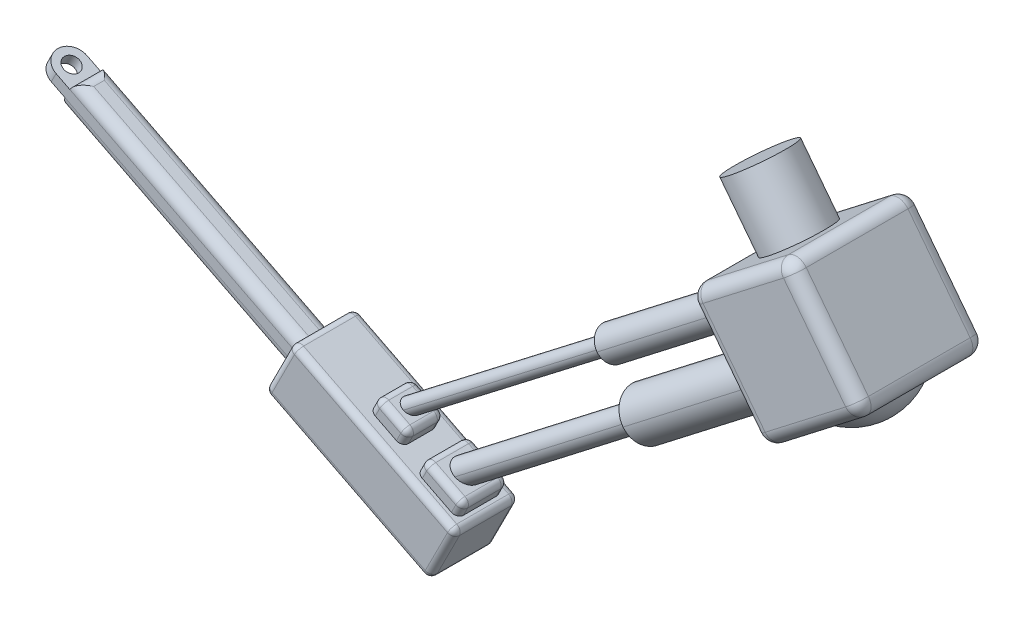
SolidWorks part; units mm, degrees
ref_plane "Front Plane" through (0, 0, 0) normal (0, 0, 1) x (1, 0, 0)
ref_plane "Top Plane" through (0, 0, 0) normal (0, 1, 0) x (1, 0, 0)
ref_plane "Right Plane" through (0, 0, 0) normal (1, 0, 0) x (0, 0, -1)
sketch "Sketch2" plane through (0, 0, 0) normal (0, 0, 1) x (1, 0, 0)
  line L0 (226.5457, 190.9655) -> (147.403, 129.839) construction
  line L1 (147.403, 129.839) -> (-96.781, -58.7584) construction
  line L2 (86.2766, 208.9817) -> (208.5294, 50.6964)
  line L3 (-96.781, -58.7584) -> (147.403, 129.839)
  line L4 (147.403, 129.839) -> (193.2478, 70.4821)
  line L5 (193.2478, 70.4821) -> (-50.9362, -118.1154)
  line L6 (208.5294, 50.6964) -> (366.8147, 172.9493)
  line L7 (-112.0626, -38.9727) -> (132.1214, 149.6247)
  line L8 (132.1214, 149.6247) -> (101.5582, 189.196)
  line L9 (101.5582, 189.196) -> (-142.6258, 0.5986)
  line L10 (366.8147, 172.9493) -> (244.5619, 331.2346)
  line L11 (244.5619, 331.2346) -> (86.2766, 208.9817)
  line L12 (-456.7039, -257.0363) -> (-470.0861, -250.2602)
  line L13 (-338.7843, -316.7457) -> (-62.3974, -103.2761)
  line L14 (-62.3974, -103.2761) -> (-50.9362, -118.1154)
  line L15 (-50.9362, -118.1154) -> (-62.3974, -103.2761)
  line L16 (-432.294, -269.3964) -> (-456.7039, -257.0363)
  line L18 (-134.985, -9.2942) -> (-142.6258, 0.5986)
  line L19 (-85.3198, -73.5976) -> (-96.781, -58.7584)
  line L20 (-112.0626, -38.9727) -> (-119.7034, -29.0799)
  line L21 (193.2478, 70.4821) -> (-50.9362, -118.1154)
  line L22 (193.2478, 70.4821) -> (-50.9362, -118.1154)
  line L23 (-62.3974, -103.2761) -> (-338.7843, -316.7457)
  line L24 (-96.781, -58.7584) -> (147.403, 129.839)
  line L26 (-62.3974, -103.2761) -> (-85.3198, -73.5976)
  line L27 (-119.7034, -29.0799) -> (-134.985, -9.2942)
  line L38 (226.5457, 190.9655) -> (231.3859, -316.7457) construction
  line L39 (-338.7843, -316.7457) -> (231.3859, -316.7457) construction
  line L41 (-85.3198, -73.5976) -> (-375.7062, -298.05)
  line L45 (-119.7034, -29.0799) -> (-432.294, -269.3964)
  line L50 (-375.7062, -298.05) -> (-389.0884, -291.2739)
  line L51 (-134.985, -9.2942) -> (-456.7039, -257.0363)
  line L52 (-456.7039, -257.0363) -> (-470.0861, -250.2602)
  line L53 (-470.0861, -250.2602) -> (-481.3797, -272.5638)
  line L54 (-481.3797, -272.5638) -> (-430.2055, -298.4763)
  line L55 (-430.2055, -298.4763) -> (-418.9118, -276.1726)
  line L56 (-418.9118, -276.1726) -> (-432.294, -269.3964)
  line L57 (-389.0884, -291.2739) -> (-400.382, -313.5775)
  line L58 (-400.382, -313.5775) -> (-336.6957, -345.8255)
  line L59 (-336.6957, -345.8255) -> (-325.4021, -323.5218)
  line L60 (-325.4021, -323.5218) -> (-338.7843, -316.7457)
  line L61 (-418.9118, -276.1726) -> (-432.294, -269.3964)
  line L63 (-338.7843, -316.7457) -> (-375.7062, -298.05)
  dimension "D2" = 50
  dimension "D3" = 75
  dimension "D4" = 50
  dimension "D5" = 37.5
  dimension "D6" = 18.75
  dimension "D7" = 25
  dimension "D8" = 12.5
  dimension "D9" = 507.7112
  dimension "D10" = 570.1702
  dimension "D11" = 15
  dimension "D12" = 15
  dimension "D13" = 15
  dimension "D17" = 25
  dimension "D18" = 25
  dimension "D19" = 25
  dimension "D20" = 15
extrude "Boss-Extrude1" add sketch "Sketch2" along normal blind 100 contours L10 L11 L2 L6 region at (226.5457, 190.9655, 0)
extrude "Boss-Extrude2" add sketch "Sketch2<3>" against normal blind 100 contours L10 L11 L2 L6 region at (226.5457, 190.9655, 0)
sketch "Sketch2<3>" plane through (0, 0, 0) normal (0, 0, 1) x (1, 0, 0) same geometry as "Sketch2"
extrude "Boss-Extrude3" add sketch "Sketch2<4>" along normal blind 25 contours L27 L20 L7 L2 L9 L18 region at (-5.2522, 75.1117, 0)
sketch "Sketch2<4>" plane through (0, 0, 0) normal (0, 0, 1) x (1, 0, 0) same geometry as "Sketch2"
extrude "Boss-Extrude4" add sketch "Sketch2<5>" along normal blind 12.5 contours L27 region at (-285.6315, -140.9012, 0)
sketch "Sketch2<5>" plane through (0, 0, 0) normal (0, 0, 1) x (1, 0, 0) same geometry as "Sketch2"
extrude "Boss-Extrude5" add sketch "Sketch2<6>" against normal blind 25 contours L27 L20 L7 L2 L9 L18 region at (-5.2522, 75.1117, 0)
sketch "Sketch2<6>" plane through (0, 0, 0) normal (0, 0, 1) x (1, 0, 0) same geometry as "Sketch2"
extrude "Boss-Extrude6" add sketch "Sketch2<7>" against normal blind 12.5 contours L27 region at (-285.6315, -140.9012, 0)
sketch "Sketch2<7>" plane through (0, 0, 0) normal (0, 0, 1) x (1, 0, 0) same geometry as "Sketch2"
extrude "Boss-Extrude7" add sketch "Sketch2<8>" along normal blind 37.5 contours L26 L14 L5 L2 L3 L19 region at (48.2334, 5.8618, 0)
sketch "Sketch2<8>" plane through (0, 0, 0) normal (0, 0, 1) x (1, 0, 0) same geometry as "Sketch2"
extrude "Boss-Extrude8" add sketch "Sketch2<9>" against normal blind 37.5 contours L26 L14 L5 L2 L3 L19 region at (48.2334, 5.8618, 0)
sketch "Sketch2<9>" plane through (0, 0, 0) normal (0, 0, 1) x (1, 0, 0) same geometry as "Sketch2"
extrude "Boss-Extrude9" add sketch "Sketch2<10>" along normal blind 18.75 contours L26 L13 region at (-215.5932, -197.753, 0)
sketch "Sketch2<10>" plane through (0, 0, 0) normal (0, 0, 1) x (1, 0, 0) same geometry as "Sketch2"
extrude "Boss-Extrude10" add sketch "Sketch2<11>" against normal blind 18.75 contours L26 L13 region at (-215.5932, -197.753, 0)
sketch "Sketch2<11>" plane through (0, 0, 0) normal (0, 0, 1) x (1, 0, 0) same geometry as "Sketch2"
sketch3d "3DSketch1"
  point P0 (182.6105, 283.386, 58.542)
ref_plane "Plane1" through (-68.8625, 89.1588, 0) normal (-0.6113, 0.7914, 0) x (0.7914, 0.6113, 0)
sketch "Sketch3" plane through (-68.8625, 89.1588, 0) normal (-0.6113, 0.7914, 0) x (0.7914, 0.6113, 0)
  line L0 (296.0246, 100) -> (296.0246, -100) construction
  line L1 (396.0246, 100) -> (196.0246, 100) construction
  line L2 (396.0246, -100) -> (196.0246, -100) construction
  line L3 (396.0246, 0) -> (196.0246, 0) construction
  line L4 (396.0246, -100) -> (396.0246, 100) construction
  line L5 (196.0246, -100) -> (196.0246, 100) construction
  circle A0 centre (296.0246, 0) radius 50
  dimension "D2" = 100
  dimension "D1" = 100
extrude "Boss-Extrude15" add sketch "Sketch3" along normal blind 100
sketch3d "3DSketch2"
  point P0 (295.099, 117.559, -29.7433)
ref_plane "Plane2" through (53.3904, -69.1265, 0) normal (0.6113, -0.7914, 0) x (0.7914, 0.6113, 0)
sketch "Sketch4" plane through (53.3904, -69.1265, 0) normal (0.6113, -0.7914, 0) x (0.7914, 0.6113, 0)
  line L0 (296.0246, 100) -> (296.0246, -100) construction
  line L1 (196.0246, 100) -> (396.0246, 100) construction
  line L2 (196.0246, -100) -> (396.0246, -100) construction
  line L3 (396.0246, 0) -> (196.0246, 0) construction
  line L4 (396.0246, 100) -> (396.0246, -100) construction
  line L5 (196.0246, 37.5) -> (196.0246, -37.5) construction
  circle A0 centre (296.0246, 0) radius 62.5
  dimension "D1" = 125
extrude "Boss-Extrude16" add sketch "Sketch4" along normal blind 25
fillet "Fillet1" radius 90 1 edges at (352.4179, 130.2412, 0)
extrude "Boss-Extrude17" add sketch "Sketch2<19>" along normal blind 28.75 contours L55 L56 L16 L12 L53 L54 region at (-450.1458, -274.3682, 0)
sketch "Sketch2<19>" plane through (0, 0, 0) normal (0, 0, 1) x (1, 0, 0) same geometry as "Sketch2"
extrude "Boss-Extrude18" add sketch "Sketch2<20>" against normal blind 28.75 contours L55 L56 L16 L12 L53 L54 region at (-450.1458, -274.3682, 0)
sketch "Sketch2<20>" plane through (0, 0, 0) normal (0, 0, 1) x (1, 0, 0) same geometry as "Sketch2"
extrude "Boss-Extrude19" add sketch "Sketch2<21>" along normal blind 35.75 contours L60 L63 L50 L57 L58 L59 region at (-362.8921, -318.5497, 0)
sketch "Sketch2<21>" plane through (0, 0, 0) normal (0, 0, 1) x (1, 0, 0) same geometry as "Sketch2"
extrude "Boss-Extrude20" add sketch "Sketch2<22>" against normal blind 35.75 contours L60 L63 L50 L57 L58 L59 region at (-362.8921, -318.5497, 0)
sketch "Sketch2<22>" plane through (0, 0, 0) normal (0, 0, 1) x (1, 0, 0) same geometry as "Sketch2"
sketch3d "3DSketch3"
  point P0 (-367.89, -330.0301, -11.4631)
ref_plane "Plane3" through (-208.0861, -410.9478, 0) normal (-0.4517, -0.8921, 0) x (0.8921, -0.4517, 0)
sketch "Sketch5" plane through (-208.0861, -410.9478, 0) normal (-0.4517, -0.8921, 0) x (0.8921, -0.4517, 0)
  line L0 (-215.5428, 35.75) -> (-144.1573, 35.75) construction
  line L1 (-129.1573, -50.75) -> (-419.1573, -50.75)
  line L2 (-129.1573, -50.75) -> (-129.1573, 50.75)
  line L3 (-129.1573, 50.75) -> (-419.1573, 50.75)
  line L4 (-419.1573, -50.75) -> (-419.1573, 50.75)
  line L5 (-215.5428, -35.75) -> (-144.1573, -35.75) construction
  line L6 (-144.1573, 35.75) -> (-144.1573, -35.75) construction
  dimension "D1" = 15
  dimension "D2" = 15
  dimension "D3" = 15
  dimension "D4" = 290
extrude "Boss-Extrude21" add sketch "Sketch5" along normal blind 97.5
sketch3d "3DSketch4"
  point P0 (-612.4046, -281.57, 34.7276)
ref_plane "Plane4" through (-373.9501, 189.3521, 0) normal (-0.8921, 0.4517, 0) x (0, 0, 1)
sketch "Sketch6" plane through (-373.9501, 189.3521, 0) normal (-0.8921, 0.4517, 0) x (0, 0, 1)
  line L0 (0, -558.1278) -> (0, -460.6278) construction
  line L1 (50.75, -558.1278) -> (-50.75, -558.1278) construction
  line L2 (28.75, -460.6278) -> (-28.75, -460.6278) construction
  line L3 (-50.75, -509.3778) -> (50.75, -509.3778) construction
  line L4 (-50.75, -558.1278) -> (-50.75, -460.6278) construction
  line L5 (50.75, -558.1278) -> (50.75, -460.6278) construction
  line L7 (-24.375, -485.0028) -> (24.375, -485.0028)
  line L8 (-24.375, -485.0028) -> (-24.375, -533.7528)
  line L9 (-24.375, -533.7528) -> (24.375, -533.7528)
  line L10 (24.375, -485.0028) -> (24.375, -533.7528)
  dimension "D1" = 24.375
  dimension "D2" = 48.75
  dimension "D3" = 24.375
  dimension "D4" = 48.75
extrude "Boss-Extrude22" add sketch "Sketch6" along normal blind 400
sketch3d "3DSketch5"
  point P0 (-828.9261, -123.9031, 9.3746)
ref_plane "Plane5" through (-219.0974, -432.6939, 0) normal (0.4517, 0.8921, 0) x (0.8921, -0.4517, 0)
sketch "Sketch7" plane through (-219.0974, -432.6939, 0) normal (0.4517, 0.8921, 0) x (0.8921, -0.4517, 0)
  line L0 (-819.1573, 24.375) -> (-843.5323, 24.375)
  line L1 (-819.1573, -24.375) -> (-819.1573, 24.375) construction
  line L2 (-819.1573, -24.375) -> (-843.5323, -24.375)
  line L3 (-819.1573, -24.375) -> (-819.1573, 24.375)
  circle A0 centre (-843.5323, 0) radius 24.375
  circle A1 centre (-843.5323, 0) radius 12.5
  dimension "D1" = 48.75
  dimension "D3" = 25
  dimension "D2" = 24.375
extrude "Boss-Extrude23" add sketch "Sketch7" against normal blind 32.75 contours A0 L2 L3 | A0 L3 L0 | A0 A1 region at (-954.7638, -60.1844, -18.9304) region at (-956.7106, -59.1986, -16.7482) region at (-954.7638, -60.1844, 18.9304)
extrude "Cut-Extrude1" cut sketch "Sketch7<3>" against normal blind 16 contours A0 L2 L3 | A0 L3 L0 | A0 A1 region at (-954.7638, -60.1844, -18.9304) region at (-956.7106, -59.1986, -16.7482) region at (-954.7638, -60.1844, 18.9304)
sketch "Sketch7<3>" plane through (-219.0974, -432.6939, 0) normal (0.4517, 0.8921, 0) x (0.8921, -0.4517, 0) same geometry as "Sketch7"
fillet "Fillet2" radius 16 6 edges at (-971.929, -106.1362, 0) (-949.9064, -62.644, 0) (-771.4769, -152.9929, -24.375) (-771.4769, -152.9929, 24.375) (-793.4995, -196.4851, 24.375) (-793.4995, -196.4851, -24.375)
fillet "Fillet3" radius 10 28 edges at (-604.0588, -265.0879, -50.75) (-496.72, -374.0831, -50.75) (-452.6749, -287.0987, -50.75) (-345.3361, -396.0939, -50.75) (-367.3586, -439.5861, 0) (-323.3135, -352.6017, 0) (-345.3361, -396.0939, 50.75) (-496.72, -374.0831, 50.75) (-604.0588, -265.0879, 50.75) (-452.6749, -287.0987, 50.75) (-394.7352, -302.4257, 35.75) (-394.7352, -302.4257, -35.75) (-389.0884, -291.2739, 0) (-357.2453, -307.3979, -35.75) (-331.0489, -334.6737, -35.75) (-325.4021, -323.5218, 0) (-357.2453, -307.3979, 35.75) (-331.0489, -334.6737, 35.75) (-424.5586, -287.3244, 28.75) (-418.9118, -276.1726, 0) (-424.5586, -287.3244, -28.75) (-444.499, -263.2164, 28.75) (-475.7329, -261.412, 28.75) (-470.0861, -250.2602, 0) (-475.7329, -261.412, -28.75) (-444.499, -263.2164, -28.75) (-582.0362, -221.5957, 0) (-626.0813, -308.5801, 0)
fillet "Fillet4" radius 12.5 4 edges at (-275.9987, -149.2381, 12.5) (-275.9987, -149.2381, -12.5) (-295.8445, -133.1653, 12.5) (-295.8445, -133.1653, -12.5)
fillet "Fillet5" radius 18.75 4 edges at (-200.5909, -210.0109, -18.75) (-200.5909, -210.0109, 18.75) (-230.513, -185.8238, -18.75) (-230.513, -185.8238, 18.75)
fillet "Fillet6" radius 25 4 edges at (-20.5338, 94.8973, -25) (-20.5338, 94.8973, 25) (10.0294, 55.326, 25) (10.0294, 55.326, -25)
fillet "Fillet7" radius 37.5 4 edges at (25.311, 35.5403, -37.5) (71.1558, -23.8167, -37.5) (71.1558, -23.8167, 37.5) (25.311, 35.5403, 37.5)
fillet "Fillet8" radius 20 12 edges at (244.5619, 331.2346, 0) (366.8147, 172.9493, 0) (287.6721, 111.8228, 100) (147.403, 129.839, 100) (165.4192, 270.1081, 100) (305.6883, 252.0919, 100) (165.4192, 270.1081, -100) (147.403, 129.839, -100) (287.6721, 111.8228, -100) (305.6883, 252.0919, -100) (86.2766, 208.9817, 0) (208.5294, 50.6964, 0)
